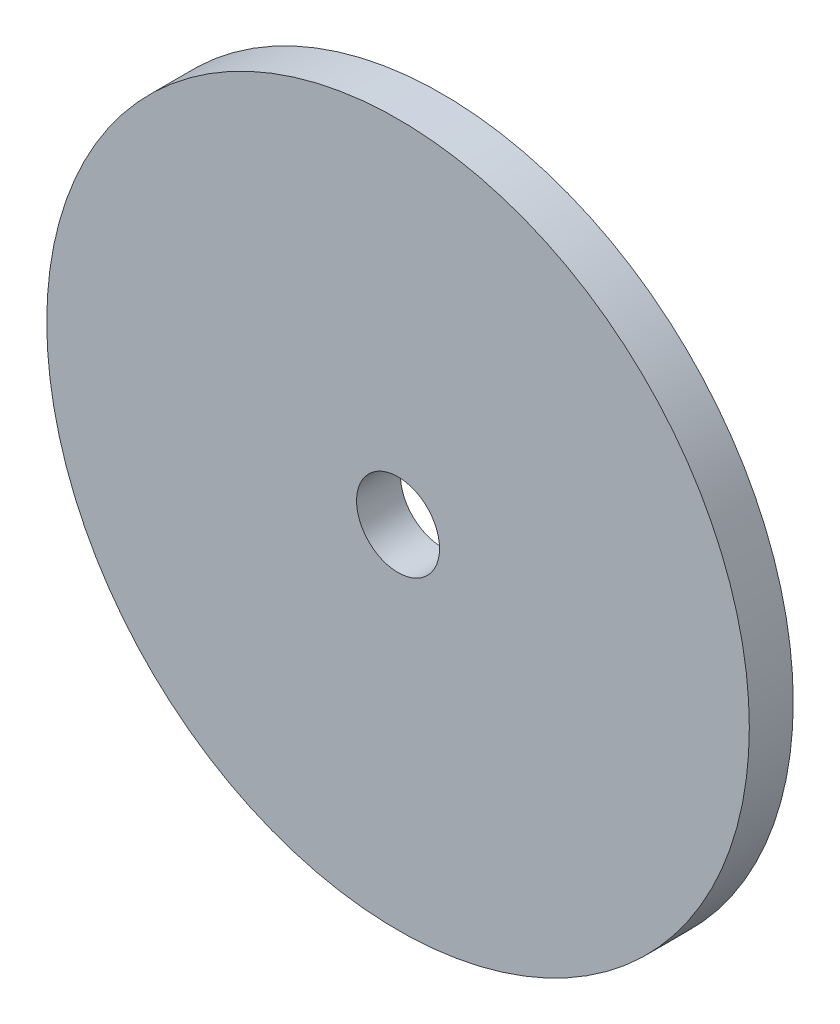
SolidWorks part; units mm, degrees
ref_plane "Front Plane" through (0, 0, 0) normal (0, 0, 1) x (1, 0, 0)
ref_plane "Top Plane" through (0, 0, 0) normal (0, 1, 0) x (1, 0, 0)
ref_plane "Right Plane" through (0, 0, 0) normal (1, 0, 0) x (0, 0, -1)
sketch "Sketch1" plane through (0, 0, 0) normal (0, 0, 1) x (1, 0, 0)
  circle A0 centre (0, 0) radius 10.16
  circle A1 centre (0, 0) radius 1.2
  dimension "D1" = 20.32
  dimension "D2" = 2.4
extrude "Boss-Extrude1" add sketch "Sketch1" along normal blind 1.27
sketch "Sketch2" plane through (0, 0, 0) normal (0, 0, -1) x (-1, 0, 0)
  line L0 (-1.524, 6.3188) -> (-1.524, 7.5888)
  line L1 (-1.524, 7.5888) -> (1.524, 7.5888)
  line L2 (1.524, 7.5888) -> (1.524, 6.3188)
  circle A0 centre (0, 0) radius 6.5
  arc A1 (-1.524, 6.3188) -> (1.524, 6.3188) centre (0, 0) cw
  point P5 (0, 7.5888)
  dimension "D1" = 13
  dimension "D2" = 1.27
  dimension "D3" = 3.048
extrude "Boss-Extrude2" add sketch "Sketch2" along normal blind 1.27 contours L2 A1 L0 L1
pattern_circular "CirPattern1" count 4 over 360 about axis through (0, 0, 1.27) along (0, 0, -1) of "Boss-Extrude2" reverse direction yes
